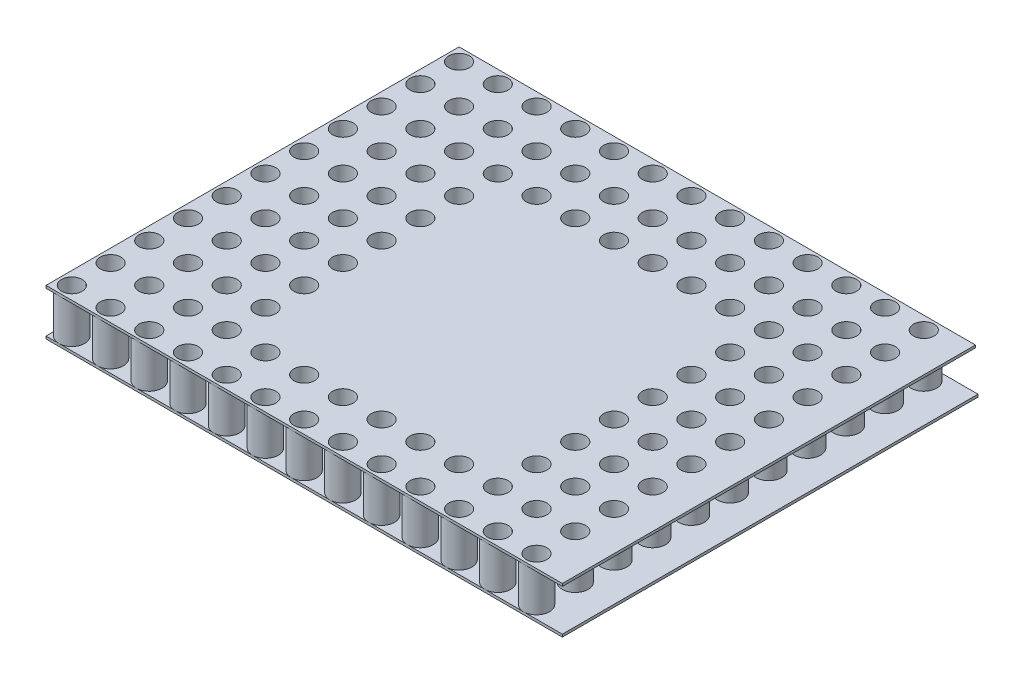
SolidWorks part; units mm, degrees
material "Copper"
ref_plane "Front Plane" through (0, 0, 0) normal (0, 0, 1) x (1, 0, 0)
ref_plane "Top Plane" through (0, 0, 0) normal (0, 1, 0) x (1, 0, 0)
ref_plane "Right Plane" through (0, 0, 0) normal (1, 0, 0) x (0, 0, -1)
sketch "Sketch1" plane through (0, 7.5115, 0) normal (0, 1, 0) x (1, 0, 0)
  line L0 (18.348, -21.0564) -> (18.348, -5.0564)
  line L1 (18.348, -5.0564) -> (38.348, -5.0564)
  line L6 (38.348, -5.0564) -> (38.348, -21.0564)
  line L7 (38.348, -21.0564) -> (18.348, -21.0564)
  dimension "D1" = 20
  dimension "D2" = 16
extrude "Boss-Extrude1" add sketch "Sketch1" along normal blind 0.1
sketch "Sketch3" plane through (0, 5.9115, 0) normal (0, -1, 0) x (-1, 0, 0)
  line L0 (-38.348, -4.9564) -> (-38.348, -21.0564)
  line L1 (-38.348, -21.0564) -> (-18.348, -21.0564)
  line L2 (-18.348, -21.0564) -> (-18.348, -4.9564)
  line L3 (-18.348, -4.9564) -> (-38.348, -4.9564)
extrude "Boss-Extrude3" add sketch "Sketch3" along normal blind 0.1
sketch "Sketch2" plane through (0, 7.5115, 0) normal (0, -1, 0) x (1, 0, 0)
  line L0 (18.348, 21.0564) -> (18.348, 5.0564) construction
  line L1 (38.348, 21.0564) -> (18.348, 21.0564) construction
  circle A0 centre (18.848, 20.5564) radius 0.4
  circle A1 centre (18.848, 20.5564) radius 0.5
  dimension "D1" = 0.1
  dimension "D2" = 1
  dimension "D3" = 0.5
  dimension "D4" = 0.5
extrude "Boss-Extrude4" add sketch "Sketch2" along normal up to surface (1.7 mm away) and the other way up to surface (0.1 mm away) contours A1 up to face at (28.348, 5.8115, 13.0064) other way up to face at (28.348, 7.6115, 13.0564)
extrude "Cut-Extrude1" cut sketch "Sketch2<5>" against normal through all and the other way through all contours A0
sketch "Sketch2<5>" plane through (0, 7.5115, 0) normal (0, -1, 0) x (1, 0, 0) same geometry as "Sketch2"
pattern_linear "LPattern1" count 11 spacing 1.5 along (0, 0, -1) count 13 spacing 1.5 along (1, 0, 0) skipping (2, 4), (2, 5), (2, 6), (2, 7), (2, 8), (2, 9), (3, 4), (3, 5), (3, 6), (3, 7), (3, 8), (3, 9), (4, 4), (4, 5), (4, 6), (4, 7), (4, 8), (4, 9), (5, 4), (5, 5), (5, 6), (5, 7), (5, 8), (5, 9), (6, 4), (6, 5), (6, 6), (6, 7), (6, 8), (6, 9), (7, 4), (7, 5), (7, 6), (7, 7), (7, 8), (7, 9) of "Boss-Extrude4", "Cut-Extrude1"
